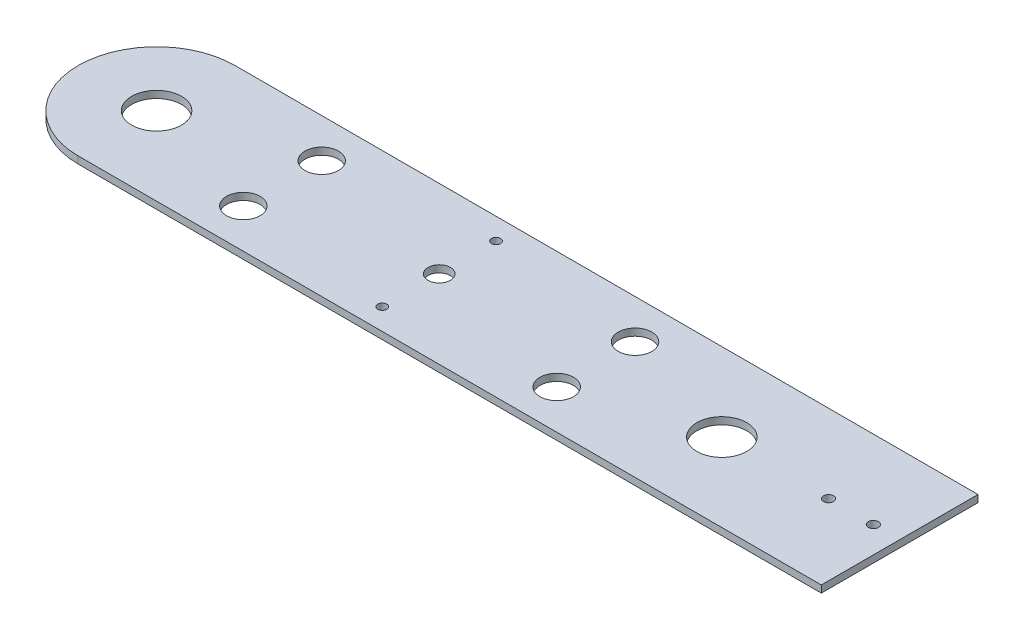
SolidWorks part; units mm, degrees
ref_plane "Front Plane" through (0, 0, 0) normal (0, 0, 1) x (1, 0, 0)
ref_plane "Top Plane" through (0, 0, 0) normal (0, 1, 0) x (1, 0, 0)
ref_plane "Right Plane" through (0, 0, 0) normal (1, 0, 0) x (0, 0, -1)
sketch "Sketch1" plane through (0, 0, 0) normal (0, 1, 0) x (1, 0, 0)
  line L0 (126.2582, 0) -> (-126.2582, 0)
  line L1 (-126.2582, 35) -> (126.2582, 35)
  line L3 (-126.2582, -35) -> (126.2582, -35)
  line L4 (-70, 35) -> (-70, 0) construction
  line L5 (-70, 0) -> (-70, -35) construction
  line L6 (70, 35) -> (70, 0) construction
  line L7 (70, 0) -> (70, -35) construction
  line L8 (0, -35) -> (0, 35) construction
  line L9 (161.2582, -35) -> (161.2582, 35) construction
  line L10 (161.2582, -35) -> (126.2582, -35)
  line L11 (161.2582, 35) -> (126.2582, 35)
  line L12 (161.2582, 0) -> (205.7082, 0) construction
  line L13 (161.2582, -35) -> (205.7082, -35)
  line L15 (161.2582, 35) -> (205.7082, 35)
  line L16 (205.7082, -35) -> (205.7082, 35)
  circle A0 centre (-126.2582, 0) radius 35
  circle A2 centre (-126.2582, 0) radius 11.15
  circle A3 centre (126.2582, 0) radius 11.15
  circle A5 centre (-70, -17.5) radius 7.5
  circle A6 centre (-70, 17.5) radius 7.5
  circle A7 centre (70, 17.5) radius 7.5
  circle A8 centre (70, -17.5) radius 7.5
  circle A9 centre (0, 0) radius 5
  circle A10 centre (0, -25.4) radius 2.02
  circle A11 centre (0, 25.4) radius 2.02
  circle A12 centre (193.9582, 0) radius 2.25
  circle A13 centre (173.9582, 0) radius 2.25
  point P4 (0, 0)
  point P38 (161.2582, 0)
  point P39 (-161.2582, 0)
  point P46 (0, 0)
  dimension "D1" = 22.3
  dimension "D2" = 10
  dimension "D3" = 70
  dimension "D4" = 15
  dimension "D7" = 25.4
  dimension "D8" = 25.4
  dimension "D9" = 4.04
  dimension "D10" = 4.04
  dimension "D13" = 4.5
  dimension "D5" = 70
  dimension "D6" = 70
  dimension "D11" = 44.45
  dimension "D12" = 322.5164
  dimension "D14" = 20
  dimension "D15" = 12.7
extrude "Boss-Extrude1" add sketch "Sketch1" along normal blind 3.175 contours A9 A3 A0 L3 L10 L13 L16 L15 L11 L1 A11 A10 A8 A7 A6 A5 | A2 A0 region at (-102.2095, 0, 24.0487) region at (-99.1105, 0, -27.1477)
